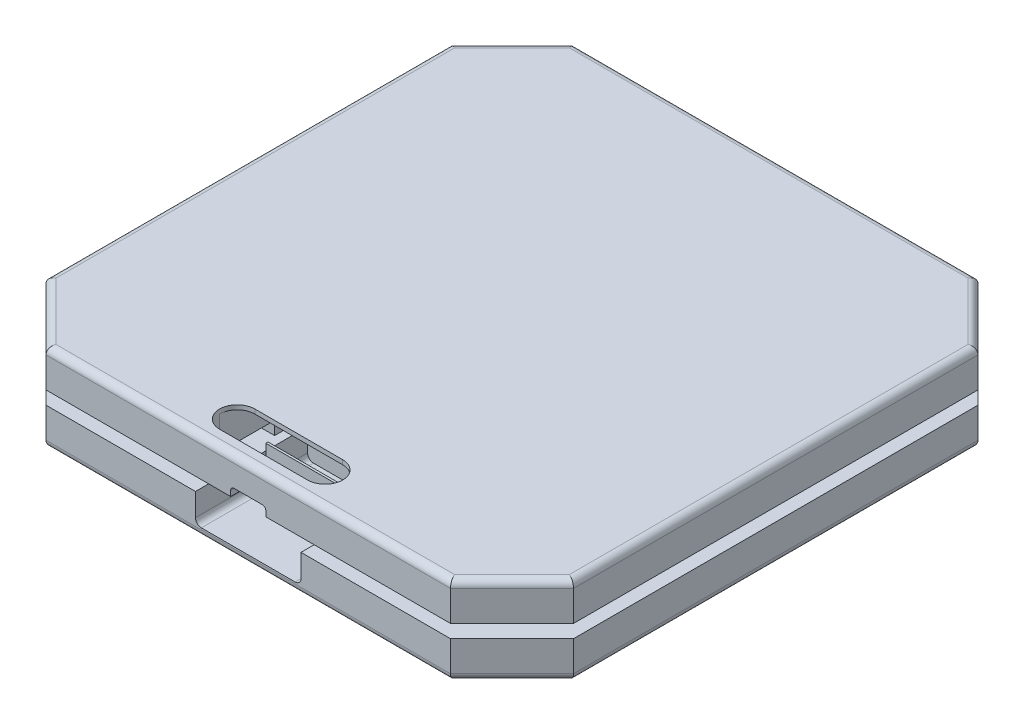
SolidWorks part; units mm, degrees
ref_plane "Plane1" through (0, 0, 0) normal (0, 0, 1) x (1, 0, 0)
ref_plane "Plane2" through (0, 0, 0) normal (0, 1, 0) x (1, 0, 0)
ref_plane "Plane3" through (0, 0, 0) normal (1, 0, 0) x (0, 0, -1)
ref_axis "Axis1" through (-80.9, 0, 0) along (1, 0, 0)
ref_axis "Axis2" through (0, 0, -80.9) along (0, 0, 1)
ref_axis "Axis3" through (0, 50, 0) along (0, -1, 0)
sketch "Sketch1" plane through (0, 0, 0) normal (0, 1, 0) x (1, 0, 0)
  line L0 (-146.05, 190.5) -> (-190.5, 146.05)
  line L1 (146.05, 190.5) -> (-146.05, 190.5)
  line L2 (190.5, 146.05) -> (190.5, -146.05)
  line L3 (146.05, -190.5) -> (-146.05, -190.5)
  line L4 (-190.5, 146.05) -> (-190.5, -146.05)
  line L5 (190.5, 190.5) -> (-190.5, -190.5) construction
  line L6 (190.5, -190.5) -> (-190.5, 190.5) construction
  line L7 (190.5, 146.05) -> (146.05, 190.5)
  line L8 (-146.05, -190.5) -> (-190.5, -146.05)
  line L9 (190.5, -146.05) -> (146.05, -190.5)
  point P0 (0, 0)
  dimension "D1" = 381
  dimension "D2" = 381
extrude "Boss-Extrude1" add sketch "Sketch1" along normal blind 63.5
ref_plane "Plane4" through (0, 0, 190.5) normal (0, 0, 1) x (1, 0, 0)
sketch "Sketch3" plane through (0, 0, 190.5) normal (0, 0, 1) x (1, 0, 0)
  line L0 (146.05, 31.75) -> (-146.05, 31.75) construction
  line L1 (146.05, 63.5) -> (146.05, 0) construction
  line L2 (-146.05, 63.5) -> (-146.05, 0) construction
  line L4 (190.5, 36.5125) -> (-190.5, 36.5125)
  line L5 (190.5, 36.5125) -> (190.5, 26.9875)
  line L6 (190.5, 26.9875) -> (-190.5, 26.9875)
  line L7 (-190.5, 36.5125) -> (-190.5, 26.9875)
  line L8 (190.5, 36.5125) -> (-190.5, 26.9875) construction
  line L9 (190.5, 26.9875) -> (-190.5, 36.5125) construction
  point P6 (0, 31.75)
  dimension "D1" = 9.525
  dimension "D2" = 381
extrude "Cut-Extrude1" cut sketch "Sketch3" against normal blind 63.5
mirror "Mirror1" about plane through (0, 0, 0) normal (0, 0, 1) of "Cut-Extrude1"
ref_plane "Plane5" through (-190.5, 0, 0) normal (-1, 0, 0) x (0, 0, 1)
sketch "Sketch4" plane through (-190.5, 0, 0) normal (-1, 0, 0) x (0, 0, 1)
  line L0 (-127, 31.75) -> (127, 31.75) construction
  line L1 (-127, 36.5125) -> (-127, 26.9875) construction
  line L2 (127, 36.5125) -> (127, 26.9875) construction
  line L4 (-190.5, 36.5125) -> (190.5, 36.5125)
  line L5 (-190.5, 36.5125) -> (-190.5, 26.9875)
  line L6 (-190.5, 26.9875) -> (190.5, 26.9875)
  line L7 (190.5, 36.5125) -> (190.5, 26.9875)
  line L8 (-190.5, 36.5125) -> (190.5, 26.9875) construction
  line L9 (-190.5, 26.9875) -> (190.5, 36.5125) construction
  point P6 (0, 31.75)
  dimension "D1" = 381
  dimension "D2" = 9.525
extrude "Cut-Extrude2" cut sketch "Sketch4" against normal blind 63.5
mirror "Mirror2" about plane through (0, 0, 0) normal (1, 0, 0) of "Cut-Extrude2"
sketch "Sketch5" plane through (0, 63.5, 0) normal (0, 1, 0) x (1, 0, 0)
  line L0 (0, -190.5) -> (0, -179.3875) construction
  line L1 (-146.05, -190.5) -> (146.05, -190.5) construction
  line L2 (0, -179.3875) -> (0, -166.6875) construction
  line L3 (31.75, -166.6875) -> (-31.75, -166.6875) construction
  line L4 (31.75, -179.3875) -> (-31.75, -179.3875)
  line L5 (31.75, -153.9875) -> (-31.75, -153.9875)
  arc A0 (31.75, -179.3875) -> (31.75, -153.9875) centre (31.75, -166.6875) ccw
  arc A1 (-31.75, -153.9875) -> (-31.75, -179.3875) centre (-31.75, -166.6875) ccw
  point P8 (0, -166.6875)
  dimension "D2" = 12.7
  dimension "D3" = 63.5
  dimension "D1" = 11.1125
extrude "Cut-Extrude3" cut sketch "Sketch5" against normal blind 31.75
sketch "Sketch6" plane through (0, 0, 190.5) normal (0, 0, 1) x (1, 0, 0)
  line L0 (0, 0) -> (0, 6.35) construction
  line L1 (-146.05, 26.9875) -> (146.05, 26.9875) construction
  line L2 (-38.1, 26.9875) -> (38.1, 26.9875)
  line L3 (-38.1, 26.9875) -> (-38.1, 10.5833)
  line L4 (-33.8667, 6.35) -> (33.8667, 6.35)
  line L5 (38.1, 26.9875) -> (38.1, 10.5833)
  line L6 (0, 26.9875) -> (0, 42.8625) construction
  line L7 (146.05, 36.5125) -> (-146.05, 36.5125) construction
  line L9 (-12.7, 36.5125) -> (12.7, 36.5125)
  line L10 (-12.7, 36.5125) -> (-12.7, 40.3225)
  line L11 (-10.16, 42.8625) -> (10.16, 42.8625)
  line L12 (12.7, 36.5125) -> (12.7, 40.3225)
  arc A0 (33.8667, 6.35) -> (38.1, 10.5833) centre (33.8667, 10.5833) ccw
  arc A1 (-38.1, 10.5833) -> (-33.8667, 6.35) centre (-33.8667, 10.5833) ccw
  arc A2 (10.16, 42.8625) -> (12.7, 40.3225) centre (10.16, 40.3225) cw
  arc A3 (-12.7, 40.3225) -> (-10.16, 42.8625) centre (-10.16, 40.3225) cw
  dimension "D3" = 4.2333
  dimension "D6" = 2.54
  dimension "D1" = 6.35
  dimension "D2" = 76.2
  dimension "D4" = 6.35
  dimension "D5" = 25.4
extrude "Cut-Extrude4" cut sketch "Sketch6" against normal blind 76.2
ref_plane "Plane6" through (0, 0, 166.6875) normal (0, 0, 1) x (1, 0, 0)
sketch "Sketch7" plane through (0, 0, 166.6875) normal (0, 0, 1) x (1, 0, 0)
  line L1 (31.75, 63.5) -> (-31.75, 63.5) construction
  line L2 (-38.1, 26.9875) -> (38.1, 26.9875)
  line L3 (-44.45, 60.325) -> (-44.45, 26.9875)
  line L4 (38.1, 26.9875) -> (-38.1, 26.9875)
  line L5 (38.1, 10.5833) -> (38.1, 26.9875)
  line L6 (-33.8667, 6.35) -> (33.8667, 6.35)
  line L7 (-38.1, 26.9875) -> (-38.1, 10.5833)
  line L8 (38.1, 26.9875) -> (-38.1, 26.9875)
  line L9 (38.1, 10.5833) -> (38.1, 26.9875)
  line L10 (-33.8667, 6.35) -> (33.8667, 6.35)
  line L11 (-38.1, 26.9875) -> (-38.1, 10.5833)
  line L12 (-44.45, 60.325) -> (44.45, 60.325)
  line L13 (-44.45, 26.9875) -> (-38.1, 26.9875)
  line L14 (44.45, 60.325) -> (44.45, 26.9875)
  line L15 (44.45, 26.9875) -> (38.1, 26.9875)
  arc A2 (33.8667, 6.35) -> (38.1, 10.5833) centre (33.8667, 10.5833) ccw
  arc A3 (-38.1, 10.5833) -> (-33.8667, 6.35) centre (-33.8667, 10.5833) ccw
  arc A4 (33.8667, 6.35) -> (38.1, 10.5833) centre (33.8667, 10.5833) ccw
  arc A5 (-38.1, 10.5833) -> (-33.8667, 6.35) centre (-33.8667, 10.5833) ccw
  dimension "D2" = 3.175
  dimension "D1" = 0
extrude "Cut-Extrude5" cut sketch "Sketch7" against normal blind 57.15 contours L11 A5 L10 A4 L9 L2 | L15 L14 L12 L3 L13 L2 region at (0, 43.6562, 166.6875) region at (0, 16.7148, 166.6875)
sketch "Sketch8" plane through (0, 0, 0) normal (0, -1, 0) x (1, 0, 0)
  line L0 (0, -190.5) -> (0, -179.3875) construction
  line L1 (0, -179.3875) -> (0, -166.6875) construction
  line L2 (31.75, -166.6875) -> (-31.75, -166.6875) construction
  line L3 (31.75, -179.3875) -> (-31.75, -179.3875)
  line L4 (31.75, -153.9875) -> (-31.75, -153.9875)
  line L5 (146.05, -190.5) -> (-146.05, -190.5) construction
  arc A0 (31.75, -179.3875) -> (31.75, -153.9875) centre (31.75, -166.6875) ccw
  arc A1 (-31.75, -153.9875) -> (-31.75, -179.3875) centre (-31.75, -166.6875) ccw
  point P5 (0, -166.6875)
  dimension "D3" = 12.7
  dimension "D1" = 11.1125
  dimension "D2" = 63.5
extrude "Cut-Extrude6" cut sketch "Sketch8" against normal blind 31.75
sketch "Sketch9" plane through (0, 0, -190.5) normal (0, 0, -1) x (-1, 0, 0)
  line L10 (0, 63.5) -> (0, 57.15) construction
  line L11 (-146.05, 63.5) -> (146.05, 63.5) construction
  line L12 (0, 36.5125) -> (0, 20.6375) construction
  line L13 (-146.05, 36.5125) -> (146.05, 36.5125) construction
  line L14 (146.05, 26.9875) -> (-146.05, 26.9875) construction
  line L15 (33.8667, 57.15) -> (-33.8667, 57.15)
  line L16 (38.1, 52.9167) -> (38.1, 36.5125)
  line L17 (38.1, 36.5125) -> (-38.1, 36.5125)
  line L18 (-38.1, 52.9167) -> (-38.1, 36.5125)
  line L19 (10.16, 20.6375) -> (-10.16, 20.6375)
  line L20 (12.7, 23.1775) -> (12.7, 26.9875)
  line L21 (12.7, 26.9875) -> (-12.7, 26.9875)
  line L22 (-12.7, 23.1775) -> (-12.7, 26.9875)
  arc A4 (-10.16, 20.6375) -> (-12.7, 23.1775) centre (-10.16, 23.1775) cw
  arc A5 (10.16, 20.6375) -> (12.7, 23.1775) centre (10.16, 23.1775) ccw
  arc A6 (-33.8667, 57.15) -> (-38.1, 52.9167) centre (-33.8667, 52.9167) ccw
  arc A7 (33.8667, 57.15) -> (38.1, 52.9167) centre (33.8667, 52.9167) cw
  point P41 (-12.7, 20.6375)
  point P44 (12.7, 20.6375)
  point P47 (-38.1, 57.15)
  point P50 (38.1, 57.15)
  dimension "D5" = 2.54
  dimension "D6" = 4.2333
  dimension "D1" = 15.875
  dimension "D2" = 6.35
  dimension "D3" = 76.2
  dimension "D4" = 25.4
extrude "Cut-Extrude7" cut sketch "Sketch9" against normal blind 76.2
ref_plane "Plane7" through (0, 0, -166.6875) normal (0, 0, -1) x (-1, 0, 0)
sketch "Sketch10" plane through (0, 0, -166.6875) normal (0, 0, -1) x (-1, 0, 0)
  line L0 (44.45, 3.175) -> (-44.45, 3.175)
  line L1 (44.45, 3.175) -> (44.45, 36.5125)
  line L2 (44.45, 36.5125) -> (38.1, 36.5125)
  line L3 (-44.45, 3.175) -> (-44.45, 36.5125)
  line L4 (-31.75, 0) -> (31.75, 0) construction
  line L12 (33.8667, 57.15) -> (-33.8667, 57.15)
  line L13 (-38.1, 52.9167) -> (-38.1, 36.5125)
  line L14 (-38.1, 36.5125) -> (38.1, 36.5125)
  line L15 (38.1, 36.5125) -> (38.1, 52.9167)
  line L16 (33.8667, 57.15) -> (-33.8667, 57.15)
  line L17 (-38.1, 52.9167) -> (-38.1, 36.5125)
  line L18 (-38.1, 36.5125) -> (38.1, 36.5125)
  line L19 (38.1, 36.5125) -> (38.1, 52.9167)
  line L20 (-44.45, 36.5125) -> (-38.1, 36.5125)
  arc A6 (-33.8667, 57.15) -> (-38.1, 52.9167) centre (-33.8667, 52.9167) ccw
  arc A7 (38.1, 52.9167) -> (33.8667, 57.15) centre (33.8667, 52.9167) ccw
  arc A8 (-33.8667, 57.15) -> (-38.1, 52.9167) centre (-33.8667, 52.9167) ccw
  arc A9 (38.1, 52.9167) -> (33.8667, 57.15) centre (33.8667, 52.9167) ccw
  dimension "D1" = 3.175
  dimension "D2" = 0
extrude "Cut-Extrude8" cut sketch "Sketch10" against normal blind 57.15 contours L20 L3 L0 L1 L2 L18 | L19 A9 L16 A8 L17 L18 region at (0, 19.8438, -166.6875) region at (0, 46.7852, -166.6875)
fillet "Fillet1" radius 5.08 16 edges at (-168.275, 0, -168.275) (0, 0, -190.5) (168.275, 0, -168.275) (190.5, 0, 0) (168.275, 0, 168.275) (-190.5, 0, 0) (-168.275, 0, 168.275) (0, 0, 190.5) (168.275, 63.5, -168.275) (0, 63.5, -190.5) (-168.275, 63.5, -168.275) (190.5, 63.5, 0) (168.275, 63.5, 168.275) (0, 63.5, 190.5) (-168.275, 63.5, 168.275) (-190.5, 63.5, 0)
ref_plane "Plane8" through (0, 0, 152.4) normal (0, 0, 1) x (1, 0, 0)
sketch "Sketch12" plane through (0, 0, 152.4) normal (0, 0, 1) x (1, 0, 0)
  line L0 (-33.8667, 6.35) -> (33.8667, 6.35) construction
  line L1 (-25.4, 6.35) -> (25.4, 6.35)
  line L2 (-25.4, 6.35) -> (-25.4, 44.45)
  line L3 (-25.4, 44.45) -> (25.4, 44.45)
  line L4 (25.4, 6.35) -> (25.4, 44.45)
  line L6 (-25.4, 6.35) -> (-38.1, 26.9875) construction
  line L7 (25.4, 6.35) -> (38.1, 26.9875) construction
  dimension "D1" = 50.8
  dimension "D2" = 38.1
extrude "Boss-Extrude2" add sketch "Sketch12" against normal blind 1.5875
sketch "Sketch13" plane through (0, 0, 152.4) normal (0, 0, 1) x (1, 0, 0)
  line L0 (0, 44.45) -> (0, 6.35) construction
  line L1 (25.4, 44.45) -> (-25.4, 44.45) construction
  line L2 (-25.4, 6.35) -> (25.4, 6.35) construction
  circle A0 centre (0, 25.4) radius 11.1125
  circle A1 centre (0, 25.4) radius 9.525
  dimension "D1" = 22.225
  dimension "D2" = 19.05
extrude "Boss-Extrude3" add sketch "Sketch13" along normal blind 12.7
sketch "Sketch15" plane through (0, 0, 152.4) normal (0, 0, 1) x (1, 0, 0)
  circle A1 centre (0, 25.4) radius 9.525
  circle A2 centre (0, 25.4) radius 9.525
  dimension "D1" = 0
extrude "Boss-Extrude4" add sketch "Sketch15" against normal blind 6.35
sketch "Sketch16" plane through (0, 0, 152.4) normal (0, 0, 1) x (1, 0, 0)
  line L0 (9.525, 25.4) -> (0, 25.4) construction
  line L1 (0, 25.4) -> (2.6941, 28.0941) construction
  line L2 (0, 25.4) -> (-2.6941, 22.7059) construction
  line L3 (-2.6941, 22.7059) -> (0, 25.4) construction
  line L4 (0, 25.4) -> (-2.6941, 28.0941) construction
  line L5 (2.6941, 22.7059) -> (0, 25.4) construction
  circle A0 centre (2.6941, 28.0941) radius 0.7937
  circle A1 centre (0, 25.4) radius 9.525 construction
  circle A2 centre (-2.6941, 28.0941) radius 0.7938
  circle A3 centre (-2.6941, 22.7059) radius 0.7938
  circle A4 centre (2.6941, 22.7059) radius 0.7938
  dimension "D1" = 1.5875
  dimension "D2" = 3.81
  dimension "D3" = 45
extrude "Boss-Extrude5" add sketch "Sketch16" along normal blind 11.43
fillet "Fillet2" radius 0.7937 4 edges at (-1.9003, 22.7059, 163.83) (3.4878, 22.7059, 163.83) (3.4878, 28.0941, 163.83) (-1.9003, 28.0941, 163.83)
sketch "Sketch17" plane through (0, 0, 0) normal (0, -1, 0) x (1, 0, 0)
  line L0 (0, 0) -> (165.1, 0) construction
  line L1 (0, 185.42) -> (0, -185.42) construction
  line L2 (143.9458, 185.42) -> (-143.9458, 185.42) construction
  line L3 (-143.9458, -185.42) -> (143.9458, -185.42) construction
  line L4 (190.5, 146.05) -> (190.5, -146.05) construction
  circle A0 centre (165.1, 0) radius 3.175
  circle A1 centre (-165.1, 0) radius 3.175
  point P9 (190.5, 0)
  dimension "D2" = 6.35
  dimension "D1" = 25.4
extrude "Cut-Extrude9" cut sketch "Sketch17" against normal blind 25.4
